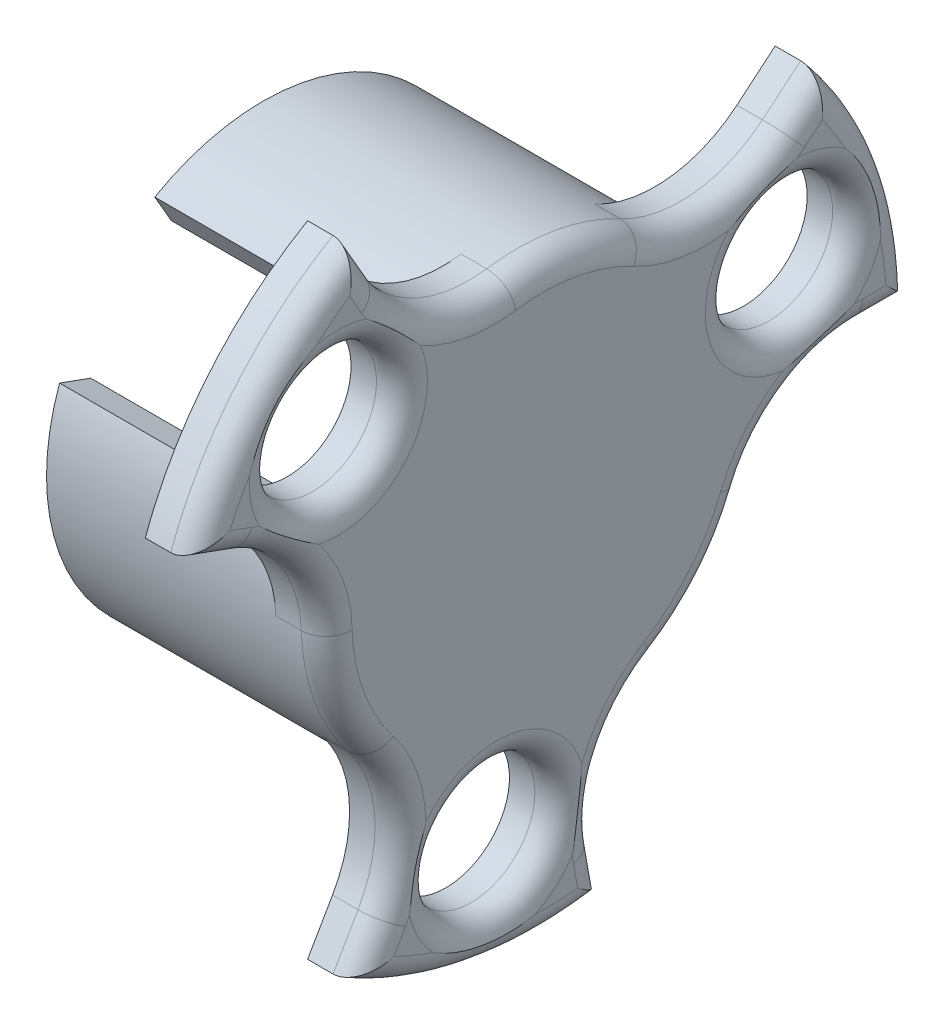
SolidWorks part; units mm, degrees
ref_plane "Front Plane" through (0, 0, 0) normal (0, 0, 1) x (1, 0, 0)
ref_plane "Top Plane" through (0, 0, 0) normal (0, 1, 0) x (1, 0, 0)
ref_plane "Right Plane" through (0, 0, 0) normal (1, 0, 0) x (0, 0, -1)
sketch "Sketch1" plane through (0, 0, 0) normal (1, 0, 0) x (0, 0, -1)
  circle A0 centre (0, 0) radius 8.5
  dimension "D1" = 17
extrude "Boss-Extrude1" add sketch "Sketch1" along normal blind 1 contours A0
sketch "Sketch2" plane through (0, 0, 0) normal (-1, 0, 0) x (0, 0, 1)
  circle A3 centre (0, 0) radius 5.375
  dimension "D1" = 10.75
extrude "Boss-Extrude2" add sketch "Sketch2" along normal blind 1.5 draft 40 contours A3
sketch "Sketch3" plane through (0, 0, 0) normal (-1, 0, 0) x (0, 0, 1)
  circle A2 centre (0, 0) radius 7.2
  circle A3 centre (0, 0) radius 7.2
  circle M3 centre (0, 0) radius 8.5
  dimension "D1" = 1.3
extrude "Boss-Extrude3" add sketch "Sketch3" along normal blind 10 contours A3 M3
sketch "Sketch6" plane through (0, 0, 0) normal (0, 1, 0) x (1, 0, 0)
  line L1 (-10, 7.2) -> (-10, -7.2) construction
  line L4 (-10, 8.5) -> (-10, 7.2)
  line L5 (-10, 8.5) -> (-10, -8.5) construction
  line L6 (-10, 7.2) -> (-1, 7.2)
  line L8 (-1, 7.2) -> (-1, 8.5)
  line L9 (-1, 8.5) -> (-10, 8.5)
  dimension "D2" = 9
sketch "Sketch7" plane through (0, 0, 0) normal (0, 1, 0) x (1, 0, 0)
  line L0 (-10, 0) -> (1, 0) construction
  line L1 (-10, 8.5) -> (-10, -8.5) construction
  line L2 (1, -8.5) -> (1, 8.5) construction
revolve "Cut-Revolve1" cut sketch "Sketch6" angle 40 about L0
pattern_circular "CirPattern1" count 3 over 360 about axis through (0, 0, 0) along (1, 0, 0) of "Cut-Revolve1"
sketch "Sketch8" plane through (0, 0, 0) normal (0, 1, 0) x (1, 0, 0)
  line L0 (-1, 8.5) -> (1, 8.5)
  line L5 (-1, 8.5) -> (-1, 14.5)
  line L6 (-1, 14.5) -> (1, 14.5)
  line L7 (1, 14.5) -> (1, 8.5)
  dimension "D1" = 6
revolve "Revolve1" add sketch "Sketch8" angle 40 about L0
sketch "Sketch9" plane through (-1, 0, 0) normal (-1, 0, 0) x (0, 0, 1)
  line L0 (0, 0) -> (-13.6255, 4.9593) construction
  circle A0 centre (-9.8668, 3.5912) radius 2.5
  arc A2 (-11.1076, 9.3204) -> (-14.5, 0) centre (0, 0) ccw construction
  dimension "D1" = 5
  dimension "D2" = 4
extrude "Cut-Extrude1" cut sketch "Sketch9" against normal blind 10 contours A0
pattern_circular "CirPattern3" count 3 over 360 about axis through (0, 0, 0) along (1, 0, 0) of "Revolve1", "Cut-Extrude1"
fillet "Fillet3" radius 5 6 edges at (0, -7.3612, 4.25) (0, -8.3709, -1.476) (0, 0, -8.5) (0, 5.4637, -6.5114) (0, 2.9072, 7.9874) (0, 7.3612, 4.25)
fillet "Fillet4" radius 1 21 edges at (1, -10.3405, -0.6767) (1, 6.7493, 5.5435) (1, -2.9072, 7.9874) (1, -11.7086, 6.76) (1, -13.3146, -2.3477) (1, -5.4637, -6.5114) (1, 0, -13.52) (1, 8.6905, -10.3569) (1, 8.3709, -1.476) (1, 4.6241, 12.7046) (1, 11.7086, 6.76) (1, -7.9997, 5.6131) (1, -9.4371, -2.5385) (1, -0.8612, -9.7345) (1, 6.9169, -6.9035) (1, 2.5201, 9.442) (1, 8.8609, 4.1214) (1, 4.9593, -13.6255) (1, 3.5912, -12.3668) (1, -14.2797, 2.5179) (1, 9.3204, 11.1076)
